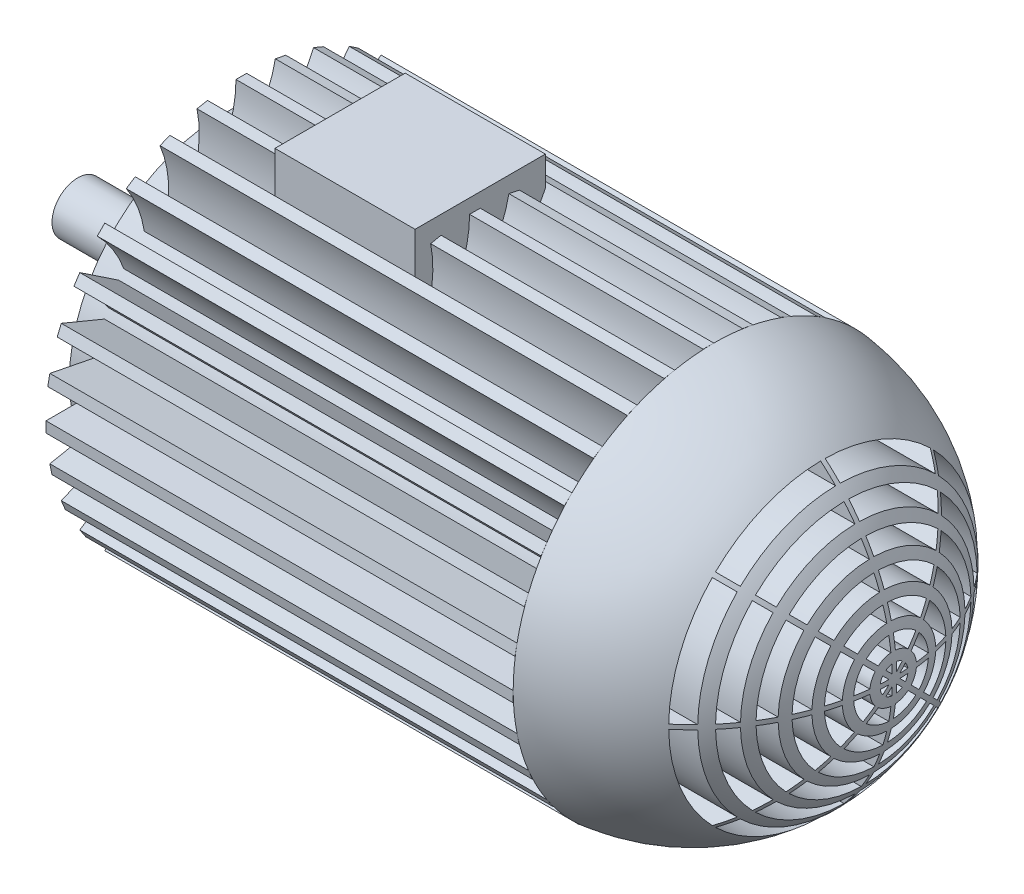
SolidWorks part; units mm, degrees
ref_plane "Front Plane" through (0, 0, 0) normal (0, 0, 1) x (1, 0, 0)
ref_plane "Top Plane" through (0, 0, 0) normal (0, 1, 0) x (1, 0, 0)
ref_plane "Right Plane" through (0, 0, 0) normal (1, 0, 0) x (0, 0, -1)
sketch "Sketch1" plane through (0, 0, 0) normal (0, 0, 1) x (1, 0, 0)
  line L0 (0, 0) -> (277.3544, 0)
  line L1 (0, 0) -> (0, 65.8814)
  line L2 (0, 65.8814) -> (200, 65.8814)
  line L3 (200, 65.8814) -> (200, 85.8814)
  arc A0 (277.3544, 0) -> (200, 85.8814) centre (191.0029, 0) ccw
  dimension "D1" = 200
  dimension "D2" = 20
  dimension "D3" = 85.8814
revolve "Revolve1" add sketch "Sketch1" angle 360 about L0
sketch "Sketch2" plane through (0, 0, 0) normal (-1, 0, 0) x (0, 0, 1)
  line L0 (0, 65.8814) -> (0, 85.8814)
  line L1 (0, 85.8814) -> (4.5519, 85.8814)
  circle A0 centre (0, 0) radius 65.8814 construction
  arc A1 (4.5519, 85.8814) -> (9.068, 65.2544) centre (53.9167, 85.8814) ccw
  arc A2 (9.068, 65.2544) -> (4.5519, 85.8814) centre (53.9167, 85.8814) cw
  circle M2 centre (0, 0) radius 65.8814
  dimension "D1" = 20
extrude "Boss-Extrude1" add sketch "Sketch2" against normal up to surface (200 mm away) contours A1 L1 L0 M2 up to face at (200, 0, 65.8814)
pattern_circular "CirPattern1" count 32 over 360 about axis through (0, 0, 0) along (1, 0, 0) of "Boss-Extrude1"
sketch "Sketch3" plane through (0, 0, 0) normal (-1, 0, 0) x (0, 0, 1)
  circle A0 centre (0, 0) radius 65.8814
extrude "Boss-Extrude2" add sketch "Sketch3" along normal blind 10
sketch "Sketch4" plane through (-10, 0, 0) normal (-1, 0, 0) x (0, 0, 1)
  circle A0 centre (0, 0) radius 11
  dimension "D1" = 22
extrude "Boss-Extrude3" add sketch "Sketch4" along normal blind 30
sketch "Sketch5" plane through (-10, 0, 0) normal (-1, 0, 0) x (0, 0, 1)
  circle A0 centre (0, 51.1865) radius 5
extrude "Cut-Extrude1" cut sketch "Sketch5" against normal blind 5
pattern_circular "CirPattern2" count 8 over 360 about axis through (0, 0, 0) along (1, 0, 0) of "Cut-Extrude1"
sketch "Sketch6" plane through (-40, 0, 0) normal (-1, 0, 0) x (0, 0, 1)
  circle A0 centre (0, 0) radius 4
extrude "Cut-Extrude2" cut sketch "Sketch6" against normal up to surface (240 mm away) up to face at (200, 32.8861, 68.1875)
ref_plane "Plane1" through (40, 0, 0) normal (-1, 0, 0) x (0, 0, 1)
sketch "Sketch7" plane through (40, 0, 0) normal (-1, 0, 0) x (0, 0, 1)
  line L1 (-27.8837, 92.0109) -> (27.8837, 92.0109)
  line L2 (-27.8837, 92.0109) -> (-27.8837, 56.1932)
  line L3 (-27.8837, 56.1932) -> (27.8837, 56.1932)
  line L4 (27.8837, 92.0109) -> (27.8837, 56.1932)
  point P0 (0, 85.8814)
extrude "Boss-Extrude4" add sketch "Sketch7" against normal blind 60
sketch "Sketch8" plane through (0, 92.0109, 0) normal (0, 1, 0) x (1, 0, 0)
  line L1 (32, 40) -> (108, 40)
  line L2 (30, 38) -> (30, -38)
  line L3 (32, -40) -> (108, -40)
  line L4 (110, 38) -> (110, -38)
  line L5 (30, 40) -> (110, -40) construction
  line L6 (30, -40) -> (110, 40) construction
  arc A0 (30, -38) -> (32, -40) centre (32, -38) ccw
  arc A1 (108, -40) -> (110, -38) centre (108, -38) ccw
  arc A2 (32, 40) -> (30, 38) centre (32, 38) ccw
  arc A3 (108, 40) -> (110, 38) centre (108, 38) cw
  point P0 (70, 0)
  dimension "D3" = 2
  dimension "D1" = 80
  dimension "D2" = 80
extrude "Boss-Extrude5" [suppressed] add sketch "Sketch8" along normal blind 40
sketch "Sketch9" [suppressed] plane through (0, 132.0109, 0) normal (0, 1, 0) x (1, 0, 0)
  line L0 (32, -40) -> (108, -40) construction
  line L1 (44, -40) -> (29, -40)
  line L2 (44, -40) -> (44, -27)
  line L3 (42, -25) -> (29, -25)
  line L4 (29, -40) -> (29, -25)
  line L5 (108, 40) -> (32, 40) construction
  line L6 (96, 40) -> (111, 40)
  line L7 (96, 40) -> (96, 27)
  line L8 (98, 25) -> (111, 25)
  line L9 (111, 40) -> (111, 25)
  line L11 (44, 40) -> (29, 40)
  line L12 (44, 40) -> (44, 27)
  line L13 (42, 25) -> (29, 25)
  line L14 (29, 40) -> (29, 25)
  line L15 (96, -40) -> (111, -40)
  line L16 (96, -40) -> (96, -27)
  line L17 (98, -25) -> (111, -25)
  line L18 (111, -40) -> (111, -25)
  arc A0 (44, 27) -> (42, 25) centre (42, 27) cw
  arc A1 (96, 27) -> (98, 25) centre (98, 27) ccw
  arc A2 (96, -27) -> (98, -25) centre (98, -27) cw
  arc A3 (44, -27) -> (42, -25) centre (42, -27) ccw
  point P16 (70, 40)
  point P17 (70, -40)
  point P24 (44, 25)
  point P27 (96, 25)
  point P32 (44, -25)
  dimension "D11" = 2
  dimension "D1" = 15
  dimension "D2" = 15
  dimension "D3" = 15
  dimension "D4" = 15
  dimension "D5" = 26
  dimension "D6" = 26
  dimension "D7" = 15
  dimension "D8" = 15
  dimension "D9" = 26
  dimension "D10" = 26
  dimension "D12" = 15
extrude "Cut-Extrude5" [suppressed] cut sketch "Sketch9" against normal blind 4
sketch "Sketch10" [suppressed] plane through (0, 128.0109, 0) normal (0, 1, 0) x (1, 0, 0)
  line L1 (38.2397, -34.2245) -> (40.2397, -33.0698)
  line L2 (40.2397, -33.0698) -> (40.2397, -30.7604)
  line L3 (40.2397, -30.7604) -> (38.2397, -29.6057)
  line L4 (38.2397, -29.6057) -> (36.2397, -30.7604)
  line L5 (36.2397, -30.7604) -> (36.2397, -33.0698)
  line L6 (36.2397, -33.0698) -> (38.2397, -34.2245)
  line L7 (102.1798, -34.1207) -> (104.1798, -32.966)
  line L8 (104.1798, -32.966) -> (104.1798, -30.6566)
  line L9 (104.1798, -30.6566) -> (102.1798, -29.5019)
  line L10 (102.1798, -29.5019) -> (100.1798, -30.6566)
  line L11 (100.1798, -30.6566) -> (100.1798, -32.966)
  line L12 (100.1798, -32.966) -> (102.1798, -34.1207)
  line L13 (101.8558, 34.0592) -> (99.8558, 32.9045)
  line L14 (99.8558, 32.9045) -> (99.8558, 30.5951)
  line L15 (99.8558, 30.5951) -> (101.8558, 29.4404)
  line L16 (101.8558, 29.4404) -> (103.8558, 30.5951)
  line L17 (103.8558, 30.5951) -> (103.8558, 32.9045)
  line L18 (103.8558, 32.9045) -> (101.8558, 34.0592)
  line L19 (37.8558, 34.0592) -> (35.8558, 32.9045)
  line L20 (35.8558, 32.9045) -> (35.8558, 30.5951)
  line L21 (35.8558, 30.5951) -> (37.8558, 29.4404)
  line L22 (37.8558, 29.4404) -> (39.8558, 30.5951)
  line L23 (39.8558, 30.5951) -> (39.8558, 32.9045)
  line L24 (39.8558, 32.9045) -> (37.8558, 34.0592)
  circle A0 centre (38.2397, -31.9151) radius 2 construction
  circle A1 centre (102.1798, -31.8113) radius 2 construction
  circle A2 centre (101.8558, 31.7498) radius 2 construction
  circle A3 centre (37.8558, 31.7498) radius 2 construction
extrude "Boss-Extrude6" [suppressed] add sketch "Sketch10" along normal blind 2 separate body
ref_plane "Plane2" through (280, 0, 0) normal (-1, 0, 0) x (0, 0, 1)
sketch "Sketch11" plane through (280, 0, 0) normal (-1, 0, 0) x (0, 0, 1)
  line L0 (-50.1737, -48.8119) -> (-2.3247, -0.9629)
  line L1 (-0.9629, -69.9934) -> (0.9629, -69.9934)
  line L2 (-0.9629, -69.9934) -> (-0.9629, -2.3247)
  line L3 (-0.9629, 69.9934) -> (0.9629, 69.9934)
  line L4 (0.9629, -69.9934) -> (0.9629, -2.3247)
  line L5 (-48.8119, -50.1737) -> (-0.9629, -2.3247)
  line L6 (-69.9934, 0.9629) -> (-2.3247, 0.9629)
  line L7 (-69.9934, -0.9629) -> (-2.3247, -0.9629)
  line L8 (-48.8119, 50.1737) -> (-0.9629, 2.3247)
  line L9 (-50.1737, 48.8119) -> (-2.3247, 0.9629)
  line L10 (0.9629, 69.9934) -> (0.9629, 2.3247)
  line L11 (-0.9629, 69.9934) -> (-0.9629, 2.3247)
  line L12 (50.1737, 48.8119) -> (2.3247, 0.9629)
  line L13 (48.8119, 50.1737) -> (0.9629, 2.3247)
  line L14 (69.9934, -0.9629) -> (2.3247, -0.9629)
  line L15 (69.9934, 0.9629) -> (2.3247, 0.9629)
  line L16 (48.8119, -50.1737) -> (0.9629, -2.3247)
  line L17 (50.1737, -48.8119) -> (2.3247, -0.9629)
  line L18 (2.3247, 0.9629) -> (69.9934, 0.9629)
  line L21 (0.9629, 2.3247) -> (0.9629, 69.9934)
  line L22 (0.9629, 2.3247) -> (48.8119, 50.1737)
  line L24 (-0.9629, 2.3247) -> (-48.8119, 50.1737)
  line L26 (-0.9629, 2.3247) -> (-0.9629, 69.9934)
  line L28 (-2.3247, 0.9629) -> (-69.9934, 0.9629)
  line L29 (-2.3247, -0.9629) -> (-50.1737, -48.8119)
  line L31 (-0.9629, -2.3247) -> (-0.9629, -69.9934)
  line L33 (0.9629, -2.3247) -> (48.8119, -50.1737)
  line L35 (0.9629, -2.3247) -> (0.9629, -69.9934)
  line L38 (2.3247, -0.9629) -> (50.1737, -48.8119)
  line L39 (-2.3247, 0.9629) -> (-50.1737, 48.8119)
  line L40 (2.3247, 0.9629) -> (50.1737, 48.8119)
  line L42 (2.3247, -0.9629) -> (69.9934, -0.9629)
  line L45 (-0.9629, -2.3247) -> (-48.8119, -50.1737)
  line L47 (-2.3247, -0.9629) -> (-69.9934, -0.9629)
  arc A0 (41.74, 43.1018) -> (0.9629, 59.9923) centre (0, 0) ccw
  arc A1 (38.9112, 40.273) -> (0.9629, 55.9917) centre (0, 0) ccw
  arc A2 (45.9832, 47.345) -> (0.9629, 65.993) centre (0, 0) ccw
  circle A3 centre (0, 0) radius 70
  arc A4 (31.8389, 33.2007) -> (0.9629, 45.9899) centre (0, 0) ccw
  arc A5 (34.6679, 36.0297) -> (0.9629, 49.9907) centre (0, 0) ccw
  arc A6 (24.7658, 26.1276) -> (0.9629, 35.9871) centre (0, 0) ccw
  arc A7 (27.5952, 28.957) -> (0.9629, 39.9884) centre (0, 0) ccw
  arc A8 (17.6913, 19.0531) -> (0.9629, 25.9822) centre (0, 0) ccw
  arc A9 (20.5214, 21.8832) -> (0.9629, 29.9845) centre (0, 0) ccw
  arc A10 (10.6123, 11.9741) -> (0.9629, 15.971) centre (0, 0) ccw
  arc A11 (13.4448, 14.8066) -> (0.9629, 19.9768) centre (0, 0) ccw
  arc A12 (3.5067, 4.8685) -> (0.9629, 5.9222) centre (0, 0) ccw
  arc A13 (6.3573, 7.7191) -> (0.9629, 9.9535) centre (0, 0) ccw
  circle A14 centre (0, 0) radius 66 construction
  circle A15 centre (0, 0) radius 60 construction
  circle A16 centre (0, 0) radius 56 construction
  circle A17 centre (0, 0) radius 50 construction
  circle A18 centre (0, 0) radius 46 construction
  circle A19 centre (0, 0) radius 40 construction
  circle A20 centre (0, 0) radius 36 construction
  circle A21 centre (0, 0) radius 30 construction
  circle A22 centre (0, 0) radius 26 construction
  circle A23 centre (0, 0) radius 20 construction
  circle A24 centre (0, 0) radius 16 construction
  circle A25 centre (0, 0) radius 10 construction
  circle A26 centre (0, 0) radius 6 construction
  arc A27 (-0.9629, 5.9222) -> (-3.5067, 4.8685) centre (0, 0) ccw
  arc A28 (-0.9629, 9.9535) -> (-6.3573, 7.7191) centre (0, 0) ccw
  arc A29 (-0.9629, 15.971) -> (-10.6123, 11.9741) centre (0, 0) ccw
  arc A30 (-4.8685, 3.5067) -> (-5.9222, 0.9629) centre (0, 0) ccw
  arc A31 (-7.7191, 6.3573) -> (-9.9535, 0.9629) centre (0, 0) ccw
  arc A32 (-11.9741, 10.6123) -> (-15.971, 0.9629) centre (0, 0) ccw
  arc A33 (-14.8066, 13.4448) -> (-19.9768, 0.9629) centre (0, 0) ccw
  arc A34 (-5.9222, -0.9629) -> (-4.8685, -3.5067) centre (0, 0) ccw
  arc A35 (-9.9535, -0.9629) -> (-7.7191, -6.3573) centre (0, 0) ccw
  arc A36 (-15.971, -0.9629) -> (-11.9741, -10.6123) centre (0, 0) ccw
  arc A37 (5.9222, 0.9629) -> (4.8685, 3.5067) centre (0, 0) ccw
  arc A38 (9.9535, 0.9629) -> (7.7191, 6.3573) centre (0, 0) ccw
  arc A39 (15.971, 0.9629) -> (11.9741, 10.6123) centre (0, 0) ccw
  arc A40 (19.9768, 0.9629) -> (14.8066, 13.4448) centre (0, 0) ccw
  arc A41 (4.8685, -3.5067) -> (5.9222, -0.9629) centre (0, 0) ccw
  arc A42 (7.7191, -6.3573) -> (9.9535, -0.9629) centre (0, 0) ccw
  arc A43 (11.9741, -10.6123) -> (15.971, -0.9629) centre (0, 0) ccw
  arc A44 (14.8066, -13.4448) -> (19.9768, -0.9629) centre (0, 0) ccw
  arc A45 (19.0531, -17.6913) -> (25.9822, -0.9629) centre (0, 0) ccw
  arc A46 (21.8832, -20.5214) -> (29.9845, -0.9629) centre (0, 0) ccw
  arc A47 (26.1276, -24.7658) -> (35.9871, -0.9629) centre (0, 0) ccw
  arc A48 (28.957, -27.5952) -> (39.9884, -0.9629) centre (0, 0) ccw
  arc A49 (33.2007, -31.8389) -> (45.9899, -0.9629) centre (0, 0) ccw
  arc A50 (36.0297, -34.6679) -> (49.9907, -0.9629) centre (0, 0) ccw
  arc A51 (40.273, -38.9112) -> (55.9917, -0.9629) centre (0, 0) ccw
  arc A52 (43.1018, -41.74) -> (59.9923, -0.9629) centre (0, 0) ccw
  arc A53 (47.345, -45.9832) -> (65.993, -0.9629) centre (0, 0) ccw
  arc A54 (0.9629, -65.993) -> (45.9832, -47.345) centre (0, 0) ccw
  arc A55 (0.9629, -59.9923) -> (41.74, -43.1018) centre (0, 0) ccw
  arc A56 (0.9629, -55.9917) -> (38.9112, -40.273) centre (0, 0) ccw
  arc A57 (0.9629, -49.9907) -> (34.6679, -36.0297) centre (0, 0) ccw
  arc A58 (0.9629, -45.9899) -> (31.8389, -33.2007) centre (0, 0) ccw
  arc A59 (0.9629, -39.9884) -> (27.5952, -28.957) centre (0, 0) ccw
  arc A60 (0.9629, -35.9871) -> (24.7658, -26.1276) centre (0, 0) ccw
  arc A61 (0.9629, -29.9845) -> (20.5214, -21.8832) centre (0, 0) ccw
  arc A62 (0.9629, -25.9822) -> (17.6913, -19.0531) centre (0, 0) ccw
  arc A63 (0.9629, -19.9768) -> (13.4448, -14.8066) centre (0, 0) ccw
  arc A64 (0.9629, -5.9222) -> (3.5067, -4.8685) centre (0, 0) ccw
  arc A65 (0.9629, -9.9535) -> (6.3573, -7.7191) centre (0, 0) ccw
  arc A66 (0.9629, -15.971) -> (10.6123, -11.9741) centre (0, 0) ccw
  arc A67 (-3.5067, -4.8685) -> (-0.9629, -5.9222) centre (0, 0) ccw
  arc A68 (-6.3573, -7.7191) -> (-0.9629, -9.9535) centre (0, 0) ccw
  arc A69 (-10.6123, -11.9741) -> (-0.9629, -15.971) centre (0, 0) ccw
  arc A70 (-13.4448, -14.8066) -> (-0.9629, -19.9768) centre (0, 0) ccw
  arc A71 (-17.6913, -19.0531) -> (-0.9629, -25.9822) centre (0, 0) ccw
  arc A72 (-20.5214, -21.8832) -> (-0.9629, -29.9845) centre (0, 0) ccw
  arc A73 (-27.5952, -28.957) -> (-0.9629, -39.9884) centre (0, 0) ccw
  arc A74 (-24.7658, -26.1276) -> (-0.9629, -35.9871) centre (0, 0) ccw
  arc A75 (-45.9832, -47.345) -> (-0.9629, -65.993) centre (0, 0) ccw
  arc A76 (-41.74, -43.1018) -> (-0.9629, -59.9923) centre (0, 0) ccw
  arc A77 (-38.9112, -40.273) -> (-0.9629, -55.9917) centre (0, 0) ccw
  arc A78 (-34.6679, -36.0297) -> (-0.9629, -49.9907) centre (0, 0) ccw
  arc A79 (-31.8389, -33.2007) -> (-0.9629, -45.9899) centre (0, 0) ccw
  arc A80 (-0.9629, 65.993) -> (-45.9832, 47.345) centre (0, 0) ccw
  arc A81 (-0.9629, 59.9923) -> (-41.74, 43.1018) centre (0, 0) ccw
  arc A82 (-0.9629, 55.9917) -> (-38.9112, 40.273) centre (0, 0) ccw
  arc A83 (-0.9629, 49.9907) -> (-34.6679, 36.0297) centre (0, 0) ccw
  arc A84 (-0.9629, 45.9899) -> (-31.8389, 33.2007) centre (0, 0) ccw
  arc A85 (-0.9629, 39.9884) -> (-27.5952, 28.957) centre (0, 0) ccw
  arc A86 (-0.9629, 35.9871) -> (-24.7658, 26.1276) centre (0, 0) ccw
  arc A87 (-0.9629, 29.9845) -> (-20.5214, 21.8832) centre (0, 0) ccw
  arc A88 (-0.9629, 25.9822) -> (-25.9822, 0.9629) centre (0, 0) ccw
  arc A89 (-0.9629, 19.9768) -> (-13.4448, 14.8066) centre (0, 0) ccw
  arc A90 (-47.345, 45.9832) -> (-65.993, 0.9629) centre (0, 0) ccw
  arc A91 (-43.1018, 41.74) -> (-59.9923, 0.9629) centre (0, 0) ccw
  arc A92 (-40.273, 38.9112) -> (-55.9917, 0.9629) centre (0, 0) ccw
  arc A93 (-36.0297, 34.6679) -> (-49.9907, 0.9629) centre (0, 0) ccw
  arc A94 (-33.2007, 31.8389) -> (-45.9899, 0.9629) centre (0, 0) ccw
  arc A95 (-28.957, 27.5952) -> (-39.9884, 0.9629) centre (0, 0) ccw
  arc A96 (-26.1276, 24.7658) -> (-35.9871, 0.9629) centre (0, 0) ccw
  arc A97 (-21.8832, 20.5214) -> (-29.9845, 0.9629) centre (0, 0) ccw
  arc A98 (-25.9822, -0.9629) -> (-19.0531, -17.6913) centre (0, 0) ccw
  arc A99 (-29.9845, -0.9629) -> (-21.8832, -20.5214) centre (0, 0) ccw
  arc A100 (-35.9871, -0.9629) -> (-26.1276, -24.7658) centre (0, 0) ccw
  arc A101 (-39.9884, -0.9629) -> (-28.957, -27.5952) centre (0, 0) ccw
  arc A102 (-45.9899, -0.9629) -> (-33.2007, -31.8389) centre (0, 0) ccw
  arc A103 (-49.9907, -0.9629) -> (-36.0297, -34.6679) centre (0, 0) ccw
  arc A104 (-55.9917, -0.9629) -> (-40.273, -38.9112) centre (0, 0) ccw
  arc A105 (-59.9923, -0.9629) -> (-43.1018, -41.74) centre (0, 0) ccw
  arc A106 (-65.993, -0.9629) -> (-47.345, -45.9832) centre (0, 0) ccw
  arc A107 (-19.9768, -0.9629) -> (-14.8066, -13.4448) centre (0, 0) ccw
  arc A108 (65.993, 0.9629) -> (47.345, 45.9832) centre (0, 0) ccw
  arc A109 (59.9923, 0.9629) -> (43.1018, 41.74) centre (0, 0) ccw
  arc A110 (55.9917, 0.9629) -> (40.273, 38.9112) centre (0, 0) ccw
  arc A111 (49.9907, 0.9629) -> (36.0297, 34.6679) centre (0, 0) ccw
  arc A112 (45.9899, 0.9629) -> (33.2007, 31.8389) centre (0, 0) ccw
  arc A113 (39.9884, 0.9629) -> (28.957, 27.5952) centre (0, 0) ccw
  arc A114 (35.9871, 0.9629) -> (26.1276, 24.7658) centre (0, 0) ccw
  arc A115 (29.9845, 0.9629) -> (21.8832, 20.5214) centre (0, 0) ccw
  arc A116 (25.9822, 0.9629) -> (19.0531, 17.6913) centre (0, 0) ccw
  point P62 (0, 0)
  dimension "D1" = 10
  dimension "D2" = 10
  dimension "D3" = 10
  dimension "D4" = 10
  dimension "D5" = 10
  dimension "D6" = 10
  dimension "D7" = 8
extrude "Cut-Extrude6" cut sketch "Sketch11" along normal up to vertex contours A81 L26 A80 L24 | A91 L39 A90 L28 | L47 A106 L29 A105 | L47 A104 L29 A103 | L47 A102 L29 A101 | L47 A100 L29 A99 | A107 L47 A98 L29 | L47 A36 L29 A35 | L47 A34 L29 | L39 A30 L28 | L26 A27 L24 | L22 A12 L21 | L18 A37 L40 | L38 A41 L42 | L35 A64 L33 | L45 A67 L31 | L38 A43 L42 A42 | L18 A39 L40 A38 | A13 L13 A10 L10 | L26 A29 L24 A28 | L39 A32 L28 A31 | L45 A69 L31 A68 | L35 A66 L33 A65 | L39 A88 L28 A33 | L45 A71 L31 A70 | A63 L35 A62 L33 | L38 A45 L42 A44 | L18 A116 L40 A40 | A11 L22 A8 L21 | A89 L26 A88 L24 | A97 L39 A96 L28 | A87 L26 A86 L24 | A115 L18 A114 L40 | A113 L18 A112 L40 | A111 L18 A110 L40 | A109 L18 A108 L40 | L38 A53 L42 A52 | L38 A51 L42 A50 | L38 A49 L42 A48 | L38 A47 L42 A46 | A55 L35 A54 L33 | A57 L35 A56 L33 | A59 L35 A58 L33 | A61 L35 A60 L33 | L5 A74 L2 A72 | L45 A79 L31 A73 | A78 L45 A77 L31 | A76 L45 A75 L31 | L22 A2 L21 A0 | A5 L13 A1 L10 | A7 L22 A4 L21 | A9 L13 A6 L10 | A83 L26 A82 L24 | A85 L26 A84 L24 | A95 L39 A94 L28 | A93 L39 A92 L28
scale "Scale1" scale about centroid uniform scaling yes scale factor 0.8
sketch "Sketch12" plane through (-9.0744, 0, 0) normal (-1, 0, 0) x (0, 0, 1)
  circle A0 centre (0.0019, 0.2467) radius 3.2 construction
  circle A1 centre (0.0019, 0.2467) radius 8.8 construction
  circle A2 centre (0.0019, 0.2467) radius 3.2
  circle A3 centre (0.0019, 0.2467) radius 8.8
extrude "Boss-Extrude7" add sketch "Sketch12" along normal blind 25.84
